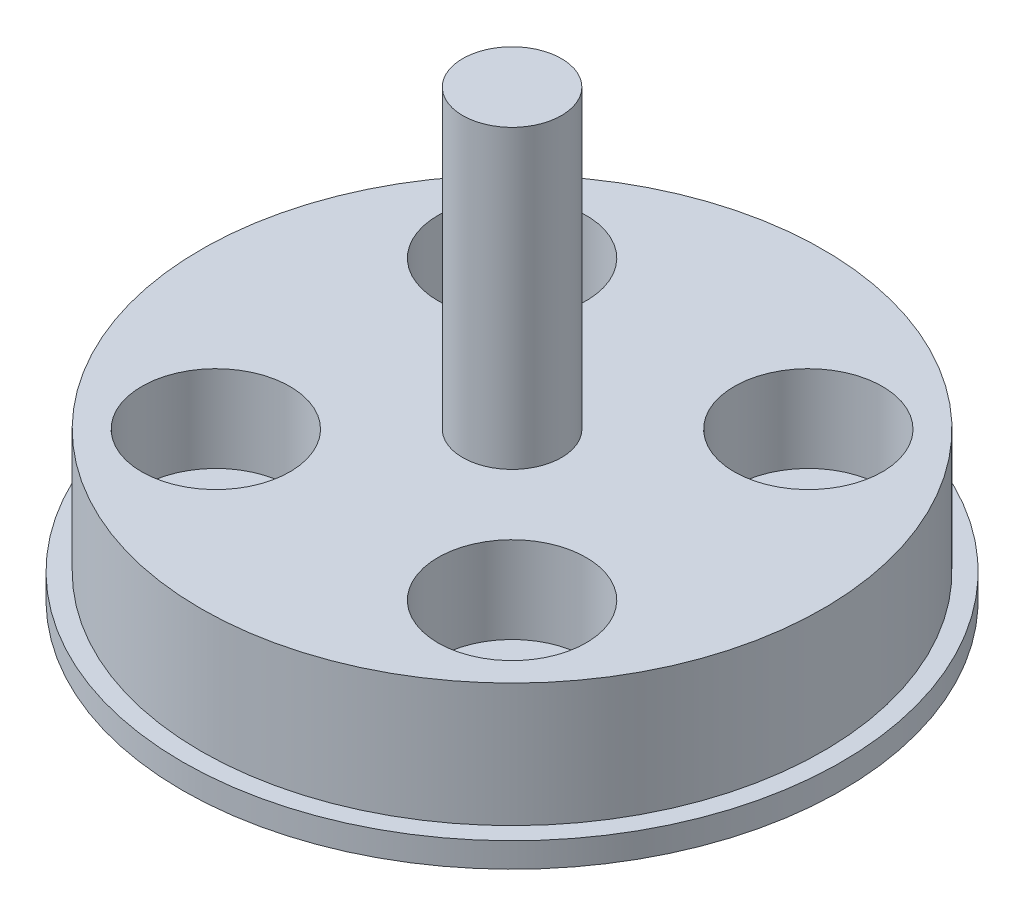
SolidWorks part; units mm, degrees
material "ABS"
ref_plane "Front Plane" through (0, 0, 0) normal (0, 0, 1) x (1, 0, 0)
ref_plane "Top Plane" through (0, 0, 0) normal (0, 1, 0) x (1, 0, 0)
ref_plane "Right Plane" through (0, 0, 0) normal (1, 0, 0) x (0, 0, -1)
sketch "Sketch1" plane through (0, 33, 0) normal (0, 1, 0) x (1, 0, 0)
  circle A0 centre (0, 0) radius 12.6
  circle A1 centre (0, 0) radius 13.35
  circle A2 centre (-6, 6) radius 1.575
  circle A3 centre (6, 6) radius 1.575
  circle A4 centre (6, -6) radius 1.575
  circle A5 centre (-6, -6) radius 1.575
  point P16 (0, 0)
  circle M2 centre (-6, -6) radius 1.575
  circle M3 centre (6, -6) radius 1.575
  circle M4 centre (6, 6) radius 1.575
  circle M5 centre (-6, 6) radius 1.575
  dimension "D1" = 3.15
  dimension "D3" = 25.2
  dimension "D4" = 26.7
  dimension "D2" = 4
extrude "Boss-Extrude1" add sketch "Sketch1" along normal blind 1 contours A0 M3 M5 M4 M2 | A1 A0 region at (0, 33, 0) region at (-12.9724, 33, 0)
extrude "Boss-Extrude2" add sketch "Sketch1<3>" along normal blind 6 contours A0 M3 M5 M4 M2 region at (0, 33, 0)
sketch "Sketch1<3>" plane through (0, 33, 0) normal (0, 1, 0) x (1, 0, 0) same geometry as "Sketch1"
sketch "Sketch2" plane through (0, 39, 0) normal (0, 1, 0) x (1, 0, 0)
  circle A0 centre (-6, 6) radius 3
  circle A1 centre (6, 6) radius 3
  circle A2 centre (6, -6) radius 3
  circle A3 centre (-6, -6) radius 3
  point P12 (0, 0)
  dimension "D1" = 6
  dimension "D2" = 4
extrude "Cut-Extrude1" cut sketch "Sketch2" against normal blind 3.5
sketch "Sketch3" plane through (0, 39, 0) normal (0, 1, 0) x (1, 0, 0)
  circle A0 centre (0, 0) radius 2
  dimension "D1" = 4
extrude "Boss-Extrude3" add sketch "Sketch3" along normal blind 12
equation "\"RingPinShaft\"= 5.05"
equation "\"CenterBearingOut\"=32.00"
equation "\"OutputBearingOut\"=50.00"
equation "\"RingPostIn\"=5.15"
equation "\"CamBearingOut\"=15.1"
equation "\"DiskOutputShaft\"=10.1"
equation "\"CenterShaft\"=25.2"
equation "\"Eccentricity\"=2"
equation "\"CycCamShaft\"=10.05"
equation "\"m3Thru\"=3.15"
equation "\"m3Insert\"=4.2"
equation "\"D1@Sketch1\"=\"m3Thru\""
equation "\"D3@Sketch1\"=\"CenterShaft\""
equation "\"D4@Sketch1\"=\"CenterShaft\"+1.5"
